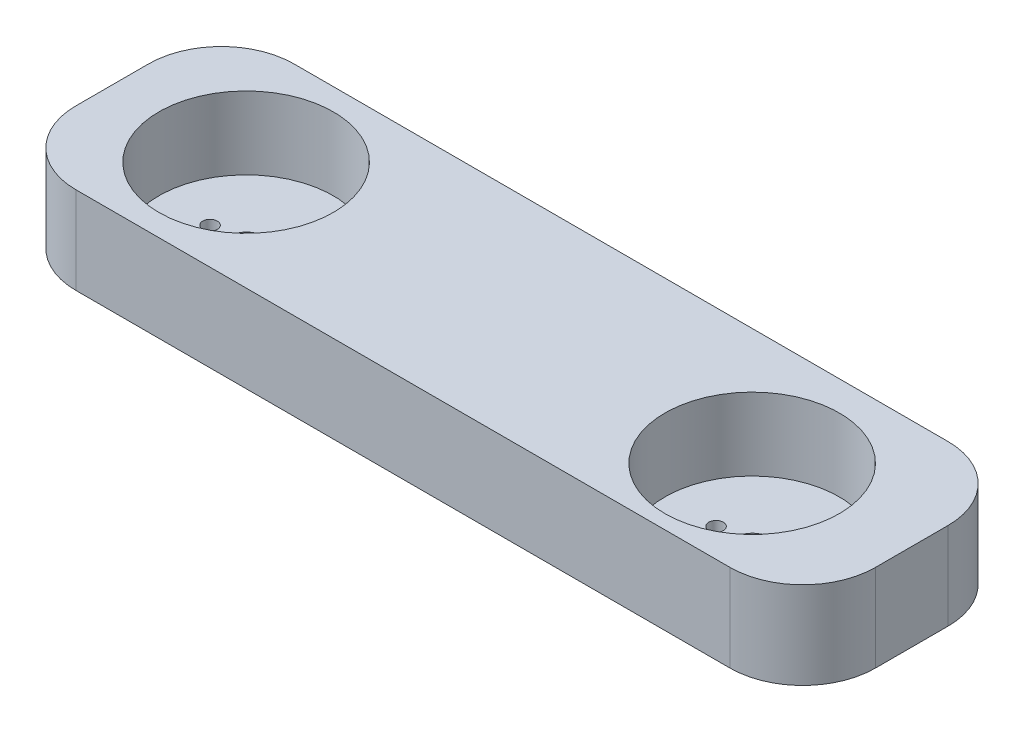
SolidWorks part; units mm, degrees
ref_plane "Front Plane" through (0, 0, 0) normal (0, 0, 1) x (1, 0, 0)
ref_plane "Top Plane" through (0, 0, 0) normal (0, 1, 0) x (1, 0, 0)
ref_plane "Right Plane" through (0, 0, 0) normal (1, 0, 0) x (0, 0, -1)
sketch "Sketch1" plane through (0, 0, 0) normal (0, 1, 0) x (1, 0, 0)
  line L1 (-49.6146, 18.5384) -> (60.3854, 18.5384)
  line L2 (-49.6146, 18.5384) -> (-49.6146, -11.4616)
  line L3 (-49.6146, -11.4616) -> (60.3854, -11.4616)
  line L4 (60.3854, 18.5384) -> (60.3854, -11.4616)
  dimension "D1" = 110
  dimension "D2" = 30
extrude "Boss-Extrude1" add sketch "Sketch1" along normal blind 12
fillet "Fillet1" radius 10 2 edges at (-49.6146, 6, -18.5384) (-49.6146, 6, 11.4616)
fillet "Fillet2" radius 10 2 edges at (60.3854, 6, -18.5384) (60.3854, 6, 11.4616)
sketch "Sketch9" plane through (0, 12, 0) normal (0, 1, 0) x (1, 0, 0)
  line L0 (-39.6146, -11.4616) -> (50.3854, -11.4616) construction
  circle A0 centre (-31.1958, 3.5384) radius 12
  dimension "D1" = 15
extrude "Cut-Extrude5" cut sketch "Sketch9" against normal blind 10
sketch "Sketch10" plane through (0, 2, 0) normal (0, 1, 0) x (1, 0, 0)
  circle A0 centre (-31.1477, 3.5384) radius 2.4
  circle A1 centre (-26.1318, 3.5384) radius 1
  circle A2 centre (-36.1636, 3.5384) radius 1
  circle A4 centre (-31.1958, 3.5384) radius 12 construction
  dimension "D1" = 12
extrude "Cut-Extrude6" cut sketch "Sketch10" against normal through all
sketch "Sketch13" plane through (70.6968, 12, 1.0722) normal (0, 1, 0) x (1, 0, 0)
  circle A0 centre (-31.1958, 3.5384) radius 12
extrude "Cut-Extrude7" cut sketch "Sketch13" against normal blind 10
sketch "Sketch15" plane through (70.6968, 2, 1.0722) normal (0, 1, 0) x (1, 0, 0)
  circle A0 centre (-31.1477, 3.5384) radius 2.4
  circle A1 centre (-26.1318, 3.5384) radius 1
  circle A2 centre (-36.1636, 3.5384) radius 1
  circle A4 centre (-31.1958, 3.5384) radius 12 construction
  dimension "D1" = 12
extrude "Cut-Extrude8" cut sketch "Sketch15" against normal through all
